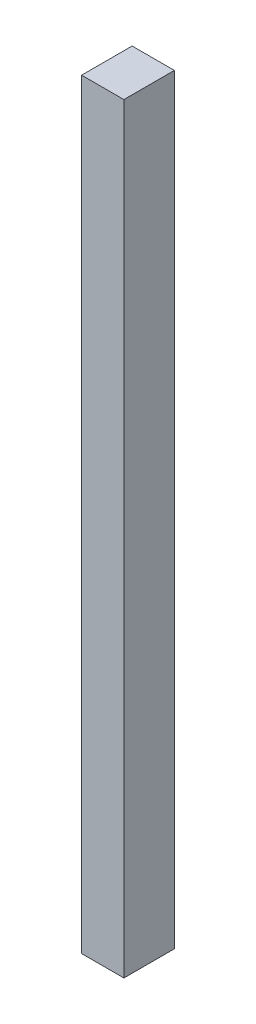
SolidWorks part; units mm, degrees
ref_plane "Front Plane" through (0, 0, 0) normal (0, 0, 1) x (1, 0, 0)
ref_plane "Top Plane" through (0, 0, 0) normal (0, 1, 0) x (1, 0, 0)
ref_plane "Right Plane" through (0, 0, 0) normal (1, 0, 0) x (0, 0, -1)
sketch "Sketch1" plane through (0, 0, 0) normal (0, 1, 0) x (1, 0, 0)
  line L1 (0, 0) -> (25.4, 0)
  line L2 (0, 0) -> (0, 30.3523)
  line L3 (0, 30.3523) -> (25.4, 30.3523)
  line L4 (25.4, 0) -> (25.4, 30.3523)
  dimension "D1" = 25.4
  dimension "D2" = 30.3523
extrude "Boss-Extrude1" add sketch "Sketch1" along normal blind 457.2
